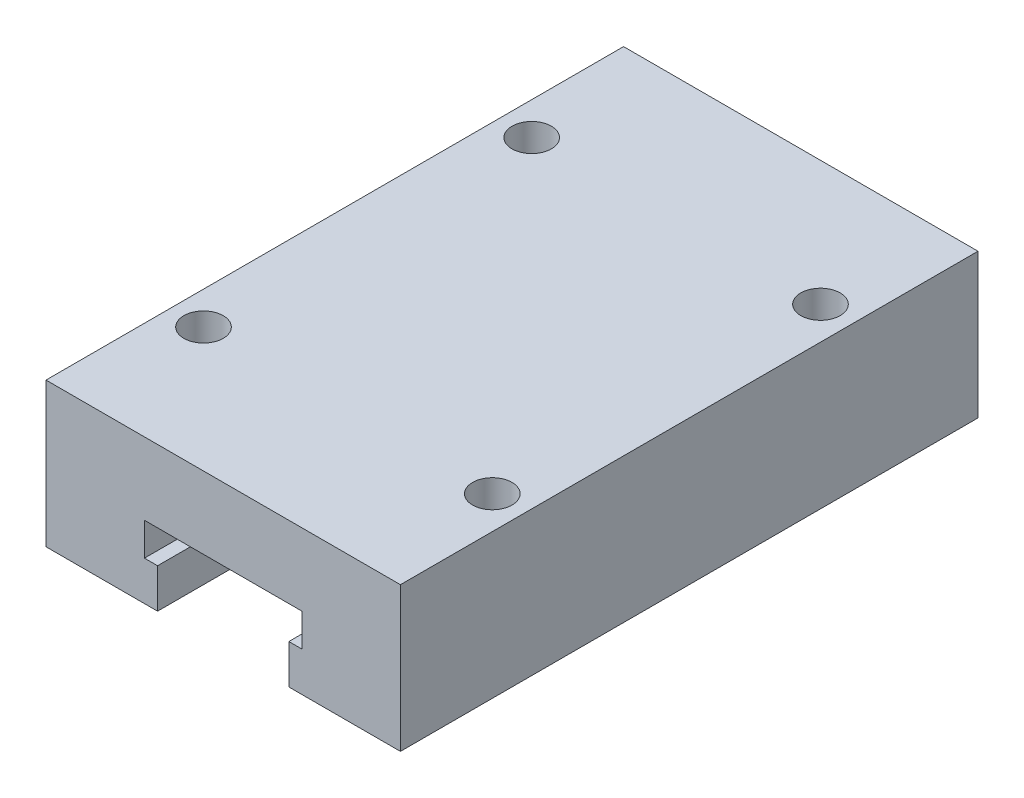
SolidWorks part; units mm, degrees
ref_plane "Front Plane" through (0, 0, 0) normal (0, 0, 1) x (1, 0, 0)
ref_plane "Top Plane" through (0, 0, 0) normal (0, 1, 0) x (1, 0, 0)
ref_plane "Right Plane" through (0, 0, 0) normal (1, 0, 0) x (0, 0, -1)
sketch "Sketch1" plane through (0, 0, 0) normal (0, 0, 1) x (1, 0, 0)
  line L0 (19.5, 5.5) -> (19.5, 3)
  line L3 (7.5, 5.5) -> (19.5, 5.5)
  line L4 (19.5, 3) -> (18.5, 3)
  line L5 (18.5, 3) -> (18.5, 0)
  line L8 (7.5, 5.5) -> (7.5, 3)
  line L9 (7.5, 3) -> (8.5, 3)
  line L10 (8.5, 3) -> (8.5, 0)
  line L13 (0, 0) -> (8.5, 0)
  line L14 (0, 0) -> (0, 11)
  line L15 (0, 11) -> (27, 11)
  line L16 (27, 11) -> (27, 0)
  line L17 (27, 0) -> (18.5, 0)
  dimension "D1" = 12
  dimension "D2" = 11
  dimension "D3" = 1
  dimension "D4" = 2.5
  dimension "D5" = 27
  dimension "D6" = 3
extrude "Boss-Extrude1" add sketch "Sketch1" along normal blind 44
sketch "Sketch2" plane through (0, 11, 0) normal (0, 1, 0) x (1, 0, 0)
  line L0 (27, -44) -> (27, 0) construction
  line L1 (0, -44) -> (0, 0) construction
  line L2 (24.5, -9.5) -> (24.5, -34.5) construction
  circle A0 centre (2.5, -9.5) radius 1.5
  circle A1 centre (24.5, -9.5) radius 1.5
  circle A2 centre (24.5, -34.5) radius 1.5
  circle A3 centre (2.5, -34.5) radius 1.5
  point P8 (27, -22)
  point P9 (24.5, -22)
  dimension "D1" = 3
  dimension "D2" = 2.5
  dimension "D3" = 2.5
  dimension "D4" = 25
extrude "Cut-Extrude1" cut sketch "Sketch2" against normal blind 4
